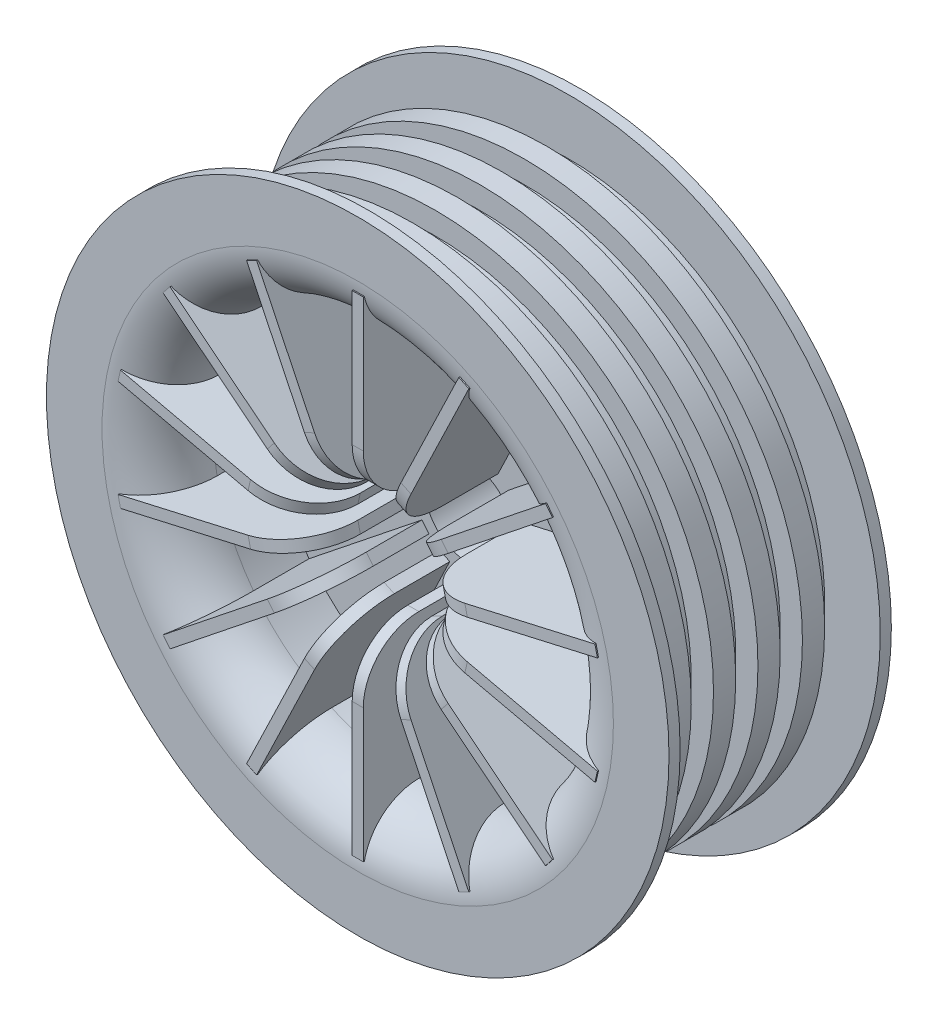
SolidWorks part; units mm, degrees
ref_plane "Front Plane" through (0, 0, 0) normal (0, 0, 1) x (1, 0, 0)
ref_plane "Top Plane" through (0, 0, 0) normal (0, 1, 0) x (1, 0, 0)
ref_plane "Right Plane" through (0, 0, 0) normal (1, 0, 0) x (0, 0, -1)
sketch "Sketch1" plane through (0, 0, 0) normal (0, 0, 1) x (1, 0, 0)
  circle A0 centre (0, 0) radius 28
  dimension "D1" = 56
extrude "Boss-Extrude1" add sketch "Sketch1" along normal blind 20
shell "Shell1" thickness 10 removed face at (28, 0, 20)
sketch "Sketch2" plane through (0, 0, 10) normal (0, 0, 1) x (1, 0, 0)
  circle A0 centre (0, 0) radius 4
  dimension "D1" = 8
extrude "Cut-Extrude1" cut sketch "Sketch2" against normal blind 20
sketch "Sketch3" plane through (0, 0, 0) normal (0, 1, 0) x (1, 0, 0)
  line L0 (28, -20) -> (28, 0) construction
  line L1 (28, -1) -> (25, -1)
  line L2 (28, -1) -> (28, -19)
  line L3 (28, -19) -> (25, -19)
  line L4 (25, -1) -> (25, -19)
  line L5 (28, 0) -> (-28, 0) construction
  line L6 (-28, -20) -> (28, -20) construction
  dimension "D1" = 1
  dimension "D2" = 1
  dimension "D3" = 3
revolve "Cut-Revolve1" cut sketch "Sketch3" angle 360 about axis through (0, 0, 20) along (0, 0, -1)
sketch "Sketch4" plane through (0, 0, 0) normal (0, 1, 0) x (1, 0, 0)
  line L1 (25, -1) -> (23, -1)
  line L2 (25, -1) -> (25, -3)
  line L3 (25, -3) -> (23, -3)
  line L4 (23, -1) -> (23, -3)
  dimension "D1" = 2
  dimension "D2" = 2
revolve "Cut-Revolve2" cut sketch "Sketch4" angle 360 about axis through (0, 0, -10) along (0, 0, 1)
pattern_linear "LPattern1" count 5 spacing 4 along (0, 0, 1) of "Cut-Revolve2"
sketch "Sketch5" plane through (0, 0, 0) normal (0, 0, -1) x (-1, 0, 0)
  circle A0 centre (0, 0) radius 18 construction
  circle A1 centre (0, 0) radius 18
  circle A2 centre (0, 0) radius 7.5
  dimension "D1" = 15
extrude "Cut-Extrude2" cut sketch "Sketch5" against normal blind 5
fillet "Fillet1" radius 5 2 edges at (18, 0, 20) (-18, 0, 0)
sketch "Sketch6" plane through (0, 0, 20) normal (0, 0, 1) x (1, 0, 0)
  line L0 (0, 5) -> (0, 22)
  dimension "D1" = 17
  dimension "D2" = 22
extrude "Extrude-Thin1" add sketch "Sketch6" against normal up to surface (10 mm away) thin up to face at (4, 0, 10) thin type mid plane wall 1
fillet "Fillet2" radius 5 1 edges at (0, 5, 20)
pattern_circular "CirPattern1" count 14 over 360 about axis through (0, 0, 10) along (0, 0, 1) of "Extrude-Thin1", "Fillet2"
sketch "Sketch7" plane through (0, 0, 0) normal (0, 0, 1) x (1, 0, 0)
  line L1 (-1, 5) -> (1, 5)
  line L2 (-1, 5) -> (-1, 3)
  line L3 (-1, 3) -> (1, 3)
  line L4 (1, 5) -> (1, 3)
  line L5 (-1, 5) -> (1, 3) construction
  line L6 (-1, 3) -> (1, 5) construction
  circle A0 centre (0, 0) radius 4 construction
  point P0 (0, 4)
  dimension "D1" = 2
  dimension "D2" = 2
extrude "Cut-Extrude3" cut sketch "Sketch7" along normal blind 19
